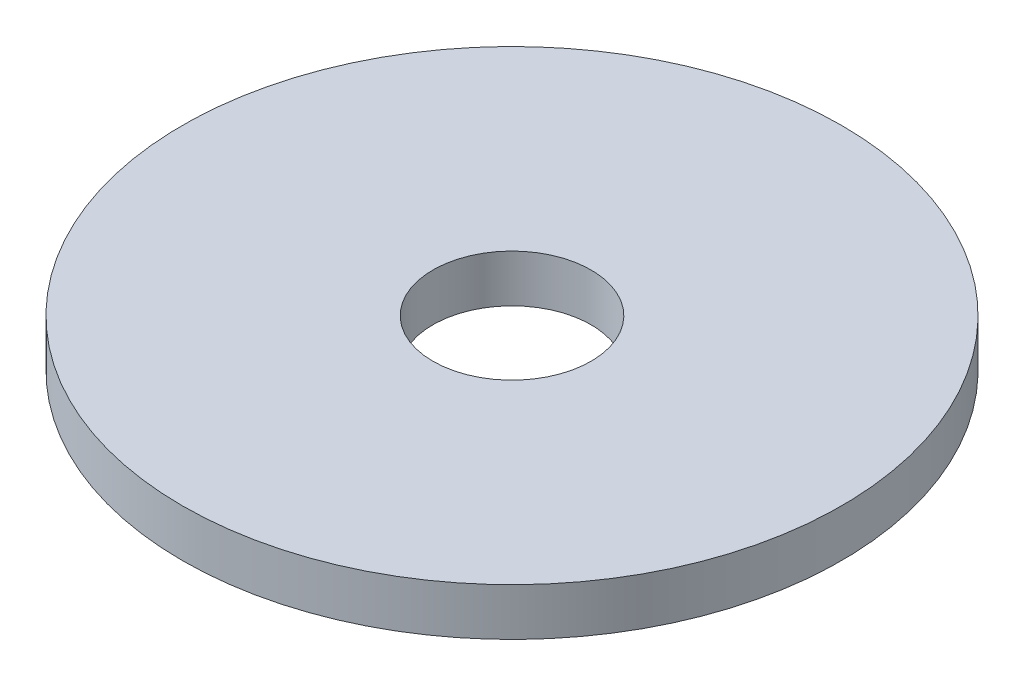
SolidWorks part; units mm, degrees
ref_plane "Front Plane" through (0, 0, 0) normal (0, 0, 1) x (1, 0, 0)
ref_plane "Top Plane" through (0, 0, 0) normal (0, 1, 0) x (1, 0, 0)
ref_plane "Right Plane" through (0, 0, 0) normal (1, 0, 0) x (0, 0, -1)
sketch "Sketch1" plane through (0, 0, 0) normal (0, 1, 0) x (1, 0, 0)
  circle A0 centre (0, 0) radius 62.5
  dimension "FLANGE_OD" = 125
extrude "Boss-Extrude1" add sketch "Sketch1" along normal blind 9
sketch "Sketch2" plane through (0, 0, 0) normal (0, 1, 0) x (1, 0, 0)
  circle A0 centre (0, 0) radius 15
  dimension "BORE_D" = 30
extrude "Cut-Extrude1" cut sketch "Sketch2" along normal through all
sketch "Sketch3" plane through (0, 9, 0) normal (0, 1, 0) x (1, 0, 0)
  circle A0 centre (0, 0) radius 9.9027 construction
  circle A1 centre (-9.9027, 0) radius 3.6254
  dimension "BOLT_D" = 7.2509
  dimension "BOLT_PCD" = 19.8054
extrude "Cut-Extrude2" cut sketch "Sketch3" against normal blind 5.5149 rebuild error yes
pattern_circular "CirPattern1" count 4 over 360 rebuild error yes
